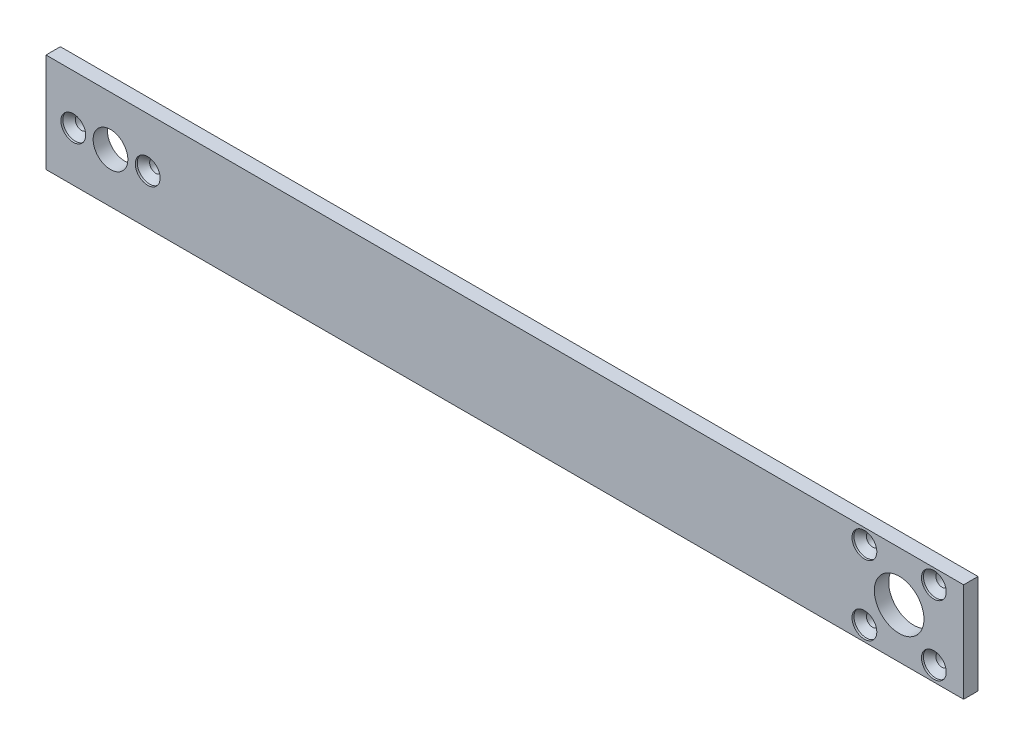
SolidWorks part; units mm, degrees
ref_plane "Front Plane" through (0, 0, 0) normal (0, 0, 1) x (1, 0, 0)
ref_plane "Top Plane" through (0, 0, 0) normal (0, 1, 0) x (1, 0, 0)
ref_plane "Right Plane" through (0, 0, 0) normal (1, 0, 0) x (0, 0, -1)
sketch "Sketch1" plane through (0, 0, 0) normal (0, 0, 1) x (1, 0, 0)
  line L1 (-92.5, 10) -> (92.5, 10)
  line L2 (-92.5, 10) -> (-92.5, -10)
  line L3 (-92.5, -10) -> (92.5, -10)
  line L4 (92.5, 10) -> (92.5, -10)
  line L5 (-92.5, 10) -> (92.5, -10) construction
  line L6 (-92.5, -10) -> (92.5, 10) construction
  point P0 (0, 0)
  dimension "D1" = 20
  dimension "D2" = 185
extrude "Base shape" add sketch "Sketch1" against normal blind 2.9
sketch "Sketch2" plane through (0, 0, 0) normal (0, 0, 1) x (1, 0, 0)
  line L0 (-89.5, 10) -> (-89.5, -10) construction
  line L1 (92.5, 10) -> (-92.5, 10) construction
  line L2 (-92.5, -10) -> (92.5, -10) construction
  line L3 (-92.5, 10) -> (-92.5, -10) construction
  line L4 (-92.5, 0) -> (92.5, 0) construction
  line L5 (92.5, -10) -> (92.5, 10) construction
  line L6 (-79.5, 10) -> (-79.5, -10) construction
  line L7 (0, 10) -> (0, -10) construction
  line L8 (79.5, 5) -> (92.5, 5) construction
  line L9 (-79.5, 3.5) -> (-92.5, 3.5) construction
  line L11 (86.5, -7) -> (72.5, -7)
  line L12 (86.5, -7) -> (86.5, 7)
  line L13 (86.5, 7) -> (72.5, 7)
  line L14 (72.5, -7) -> (72.5, 7)
  line L15 (86.5, -7) -> (72.5, 7) construction
  line L16 (86.5, 7) -> (72.5, -7) construction
  circle A0 centre (-79.5, 0) radius 10
  circle A1 centre (-87, 0) radius 1.25
  circle A2 centre (-72, 0) radius 1.25
  circle A3 centre (-79.5, 0) radius 3.5
  circle A4 centre (79.5, 0) radius 5
  circle A5 centre (72.5, 7) radius 1.25
  circle A6 centre (86.5, 7) radius 1.25
  circle A7 centre (86.5, -7) radius 1.25
  circle A8 centre (72.5, -7) radius 1.25
  dimension "D2" = 20
  dimension "D3" = 2.5
  dimension "D4" = 15
  dimension "D5" = 7
  dimension "D6" = 10
  dimension "D8" = 2.5
  dimension "D1" = 3
  dimension "D7" = 14
extrude "Motor cutouts" cut sketch "Sketch2" against normal up to next contours A5 | A6 | A7 | A8 | A1 | A2 | A3 | A4
hole_wizard "CSK for M2.5 Flat Head Machine Screw1" positions "Sketch3" profile "Sketch4" countersink size "M2.5" standard "ANSI Metric" end condition through all
sketch "Sketch3" plane through (0, 0, 0) normal (0, 0, 1) x (1, 0, 0)
  point P0 (-87, 0)
  point P3 (-72, 0)
  point P7 (72.5, 7)
  point P10 (86.5, 7)
  point P13 (72.5, -7)
  point P16 (86.5, -7)
sketch "Sketch4" plane through (-87, 0, 0) normal (1, 0, 0) x (0, -1, 0)
  line L0 (0, 0) -> (0, 2.9)
  line L1 (0, 2.9) -> (1.25, 2.9)
  line L2 (1.25, 2.9) -> (1.25, 1.65)
  line L3 (1.25, 1.65) -> (2.5, 0.4)
  line L4 (2.5, 0.4) -> (2.5, 0)
  line L6 (2.5, 0) -> (0, 0)
  line L7 (-1.25, 1.65) -> (-2.5, 0.4) construction
  line L11 (0, -6.35) -> (0, 107.95) construction
  dimension "Thru Hole Dia." = 2.5
  dimension "Thru Hole Depth" = 2.9
  dimension "C'Sink Dia." = 5
  dimension "C'Sink Angle" = 90
  dimension "Head Clearance" = 0.4
